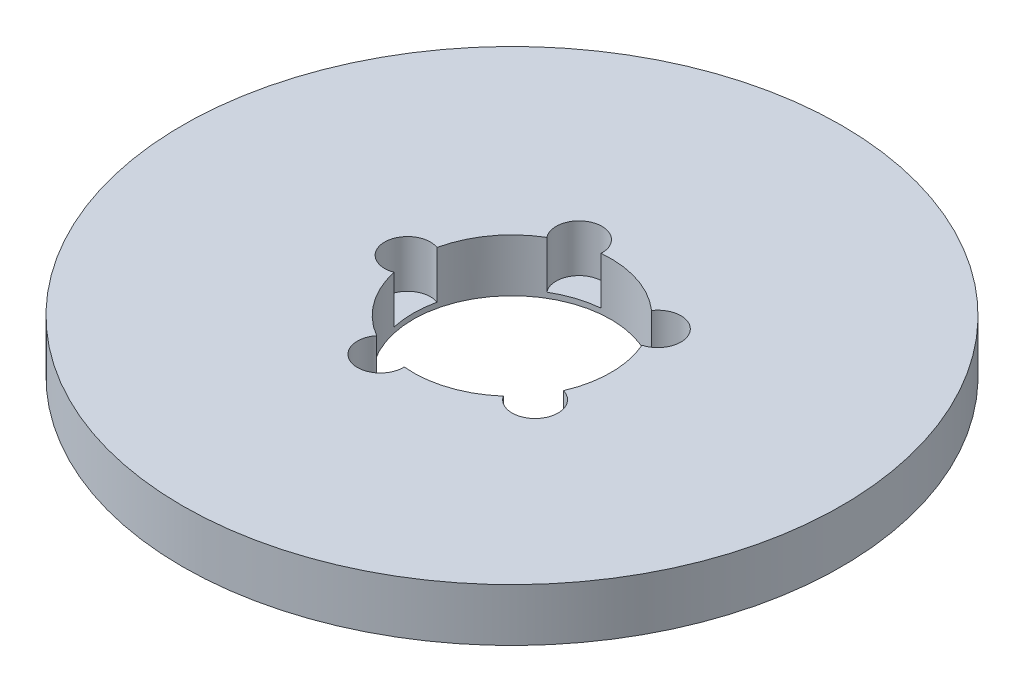
SolidWorks part; units mm, degrees
ref_plane "Front Plane" through (0, 0, 0) normal (0, 0, 1) x (1, 0, 0)
ref_plane "Top Plane" through (0, 0, 0) normal (0, 1, 0) x (1, 0, 0)
ref_plane "Right Plane" through (0, 0, 0) normal (1, 0, 0) x (0, 0, -1)
sketch "Sketch1" plane through (0, 0, 0) normal (0, 1, 0) x (1, 0, 0)
  circle A0 centre (0, 0) radius 25
  dimension "FLANGE_OD" = 50
extrude "Boss-Extrude1" add sketch "Sketch1" along normal blind 4
sketch "Sketch2" plane through (0, 0, 0) normal (0, 1, 0) x (1, 0, 0)
  circle A0 centre (0, 0) radius 7.5
  dimension "BORE_D" = 15
extrude "Cut-Extrude1" cut sketch "Sketch2" along normal through all
sketch "Sketch3" plane through (0, 4, 0) normal (0, 1, 0) x (1, 0, 0)
  circle A0 centre (0, 0) radius 7.9239 construction
  circle A1 centre (-7.9239, 0) radius 1.7407
  dimension "BOLT_D" = 3.4815
  dimension "BOLT_PCD" = 15.8478
extrude "Cut-Extrude2" cut sketch "Sketch3" against normal blind 3.5979
pattern_circular "CirPattern1" count 5 over 360 about axis through (0, 0, 0) along (0, 1, 0) of "Cut-Extrude2"
